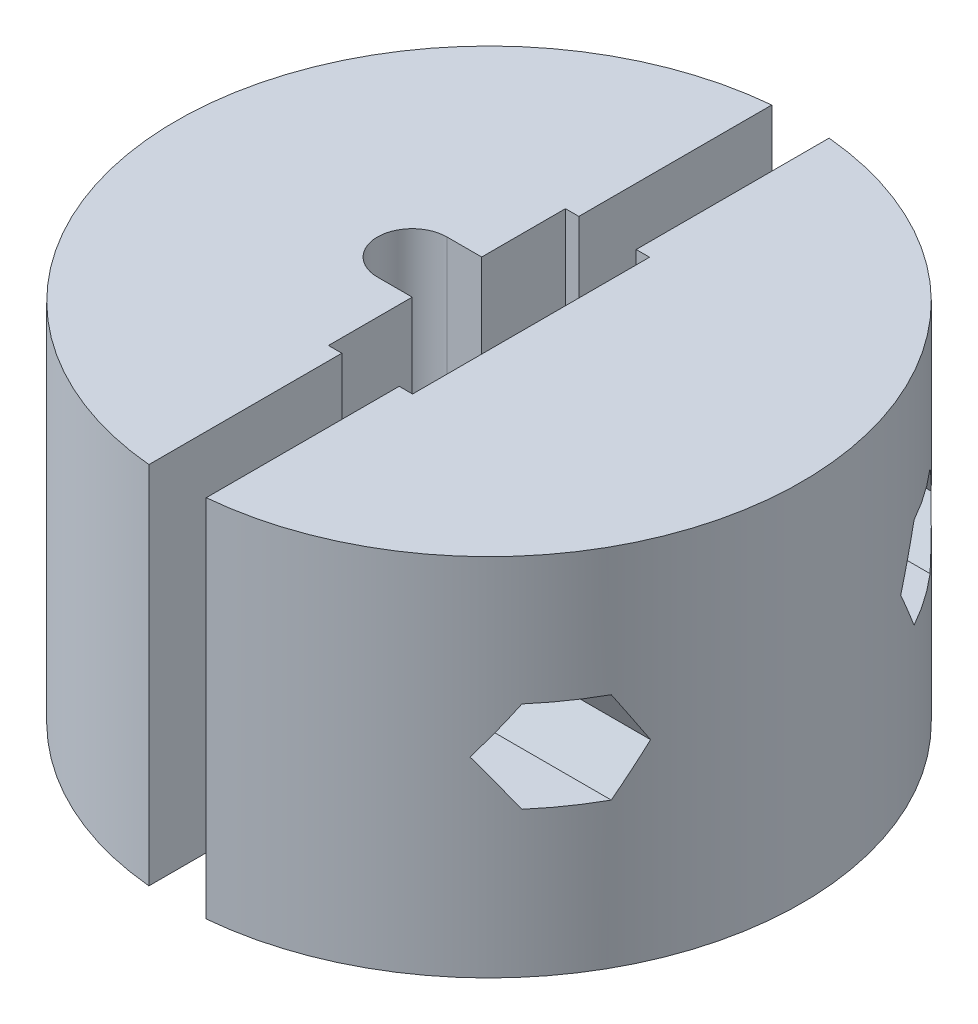
SolidWorks part; units mm, degrees
other "Markup1"
sketch "Sketch10" plane through (18, 21, 18) normal (0.9396, 0.3399, 0.0409) x (0.0435, 0, -0.9991)
ref_plane "Front Plane" through (0, 0, 0) normal (0, 0, 1) x (1, 0, 0)
ref_plane "Top Plane" through (0, 0, 0) normal (0, 1, 0) x (1, 0, 0)
ref_plane "Right Plane" through (0, 0, 0) normal (1, 0, 0) x (0, 0, -1)
sketch "Sketch1" plane through (0, 0, 0) normal (0, 1, 0) x (1, 0, 0)
  circle A0 centre (0, 0) radius 18
  dimension "D1" = 36
extrude "Boss-Extrude1" add sketch "Sketch1" along normal blind 21 contours A0
sketch "Sketch5" plane through (0, 0, 0) normal (0, -1, 0) x (-1, 0, 0)
  line L0 (-12, -2.25) -> (-12, 2.25) construction
  line L1 (-12, -2.25) -> (-12, 2.25)
  arc A0 (-12, -2.25) -> (-12, 2.25) centre (-12, 0) ccw
  dimension "D1" = 12
  dimension "D2" = 4.5
revolve "Cut-Revolve2" cut sketch "Sketch5" angle 360 about L0
ref_plane "Plane1" through (-18, 0, 0) normal (-1, 0, 0) x (0, 0, 1)
ref_plane "Plane2" through (18, 0, 0) normal (1, 0, 0) x (0, 0, -1)
sketch "Sketch6" plane through (0, 21, 0) normal (0, 1, 0) x (1, 0, 0)
  line L0 (-4.42, 2) -> (-2.42, 2)
  line L1 (-2.42, 6.82) -> (2.42, 6.82)
  line L2 (-2.42, 6.82) -> (-2.42, 2)
  line L3 (-2.42, -6.82) -> (2.42, -6.82)
  line L4 (2.42, 6.82) -> (2.42, -6.82)
  line L5 (-2.42, 6.82) -> (2.42, -6.82) construction
  line L6 (-2.42, -6.82) -> (2.42, 6.82) construction
  line L7 (-4.42, -2) -> (-2.42, -2)
  line L8 (-2.42, -2) -> (-2.42, -6.82)
  arc A0 (-4.42, 2) -> (-4.42, -2) centre (-4.42, 0) ccw
  point P0 (0, 0)
  dimension "D3" = 2
  dimension "D1" = 13.64
  dimension "D2" = 4.84
  dimension "D5" = 2
  dimension "D4" = 6.82
extrude "Cut-Extrude1" cut sketch "Sketch6" against normal through all both and the other way through all
sketch "Sketch7" plane through (-18, 0, 0) normal (-1, 0, 0) x (0, 0, 1)
  line L0 (0, 0) -> (0, 21.1129) construction
  circle A0 centre (-10.23, 11) radius 1.5
  circle A1 centre (10.23, 11) radius 1.5
  dimension "D1" = 3
  dimension "D2" = 10.23
  dimension "D3" = 11
extrude "Cut-Extrude2" cut sketch "Sketch7" against normal through all both and the other way through all
sketch "Sketch8" plane through (-18, 0, 0) normal (-1, 0, 0) x (0, 0, 1)
  circle A0 centre (-10.23, 11) radius 2.5
  circle A1 centre (10.23, 11) radius 2.5
  dimension "D1" = 5
extrude "Cut-Extrude3" cut sketch "Sketch8" against normal blind 11
sketch "Sketch9" plane through (18, 0, 0) normal (1, 0, 0) x (0, 0, -1)
  line L1 (-8.7145, 13.625) -> (-11.7455, 13.625)
  line L2 (-11.7455, 13.625) -> (-13.2611, 11)
  line L3 (-13.2611, 11) -> (-11.7455, 8.375)
  line L4 (-11.7455, 8.375) -> (-8.7145, 8.375)
  line L5 (-8.7145, 8.375) -> (-7.1989, 11)
  line L6 (-7.1989, 11) -> (-8.7145, 13.625)
  line L7 (11.7455, 13.625) -> (8.7145, 13.625)
  line L8 (8.7145, 13.625) -> (7.1989, 11)
  line L9 (7.1989, 11) -> (8.7145, 8.375)
  line L10 (8.7145, 8.375) -> (11.7455, 8.375)
  line L11 (11.7455, 8.375) -> (13.2611, 11)
  line L12 (13.2611, 11) -> (11.7455, 13.625)
  circle A0 centre (-10.23, 11) radius 2.625 construction
  circle A1 centre (10.23, 11) radius 2.625 construction
  dimension "D1" = 5.25
extrude "Cut-Extrude4" cut sketch "Sketch9" against normal blind 11
sketch "Sketch14" plane through (0, 21, 0) normal (0, 1, 0) x (1, 0, 0)
  line L0 (2.42, -6.82) -> (2.42, 6.82) construction
  line L1 (-1.65, 18) -> (1.65, 18)
  line L2 (-1.65, 18) -> (-1.65, -18)
  line L3 (-1.65, -18) -> (1.65, -18)
  line L4 (1.65, 18) -> (1.65, -18)
  line L5 (-2.42, 6.82) -> (-2.42, 2) construction
  line L6 (2.42, -6.82) -> (2.42, 6.82)
  line L7 (-2.42, 6.82) -> (-2.42, 2)
  line L8 (1.65, 0) -> (-1.65, 0) construction
  line L9 (0, 18) -> (0, -18) construction
  line M9 (2.42, -6.82) -> (-2.42, -6.82)
  line M15 (-2.42, 6.82) -> (2.42, 6.82)
  circle M16 centre (0, 0) radius 18
  dimension "D1" = 36
  dimension "D2" = 3.3
extrude "Cut-Extrude7" cut sketch "Sketch14" against normal through all contours L4 L2 M16 M15 | L4 L2 M9 M16 region at (0, 21, -12.3974) region at (0, 21, 12.3974)
equation "\"stopper_dia\"= 36mm"
equation "\"shaft_dia\"= 29mm"
equation "\"D1@Sketch1\"=\"stopper_dia\""
equation "\"led_width\"= 12.4mm"
equation "\"led_height\"= 4.4mm"
equation "\"nut_depth\"= 5mm"
equation "\"D1@Sketch6\" = \"led_width\" * 1.10"
equation "\"D2@Sketch6\"= \"led_height\" * 1.10"
equation "\"length\"= 21mm"
equation "\"D3@Sketch7\"= \"length\" - 10mm"
equation "\"D1@Boss-Extrude1\"=\"length\""
equation "\"D4@Sketch6\"= \"D1@Sketch6\" / 2"
equation "\"D2@Sketch7\"=\"D1@Sketch6\"/2*1.5"
equation "\"D1@Sketch14\"=\"stopper_dia\""
equation "\"D2@Sketch14\"=\"led_height\"*0.75"
